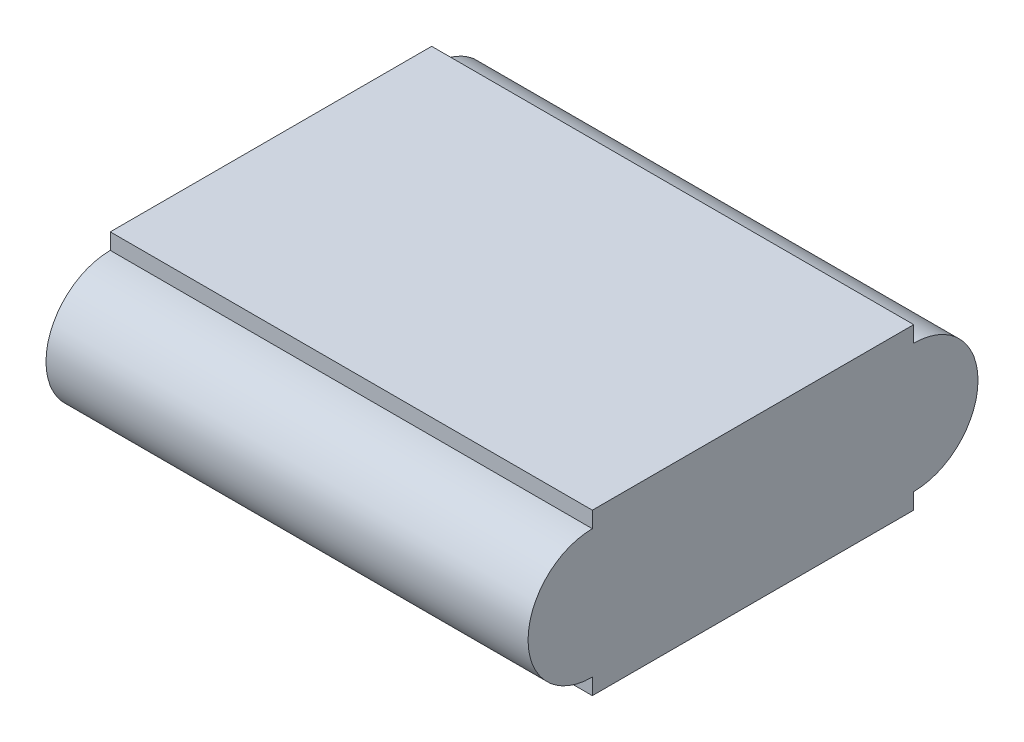
SolidWorks part; units mm, degrees
ref_plane "Front Plane" through (0, 0, 0) normal (0, 0, 1) x (1, 0, 0)
ref_plane "Top Plane" through (0, 0, 0) normal (0, 1, 0) x (1, 0, 0)
ref_plane "Right Plane" through (0, 0, 0) normal (1, 0, 0) x (0, 0, -1)
sketch "Sketch1" plane through (0, 0, 0) normal (0, 1, 0) x (1, 0, 0)
  line L1 (150, -100) -> (-150, -100)
  line L2 (150, -100) -> (150, 100)
  line L3 (150, 100) -> (-150, 100)
  line L4 (-150, -100) -> (-150, 100)
  line L5 (150, -100) -> (-150, 100) construction
  line L6 (150, 100) -> (-150, -100) construction
  point P0 (0, 0)
  dimension "D1" = 300
  dimension "D2" = 200
extrude "Boss-Extrude2" add sketch "Sketch1" along normal blind 100
sketch "Sketch2" plane through (-150, 0, 0) normal (-1, 0, 0) x (0, 0, 1)
  line L0 (100, 100) -> (100, 0) construction
  line L1 (-100, 100) -> (-100, 0) construction
  circle A0 centre (100, 50) radius 40
  circle A1 centre (-100, 50) radius 40
  dimension "D1" = 80
extrude "Boss-Extrude3" add sketch "Sketch2" against normal up to surface (300 mm away) up to face at (150, 50, 0)
